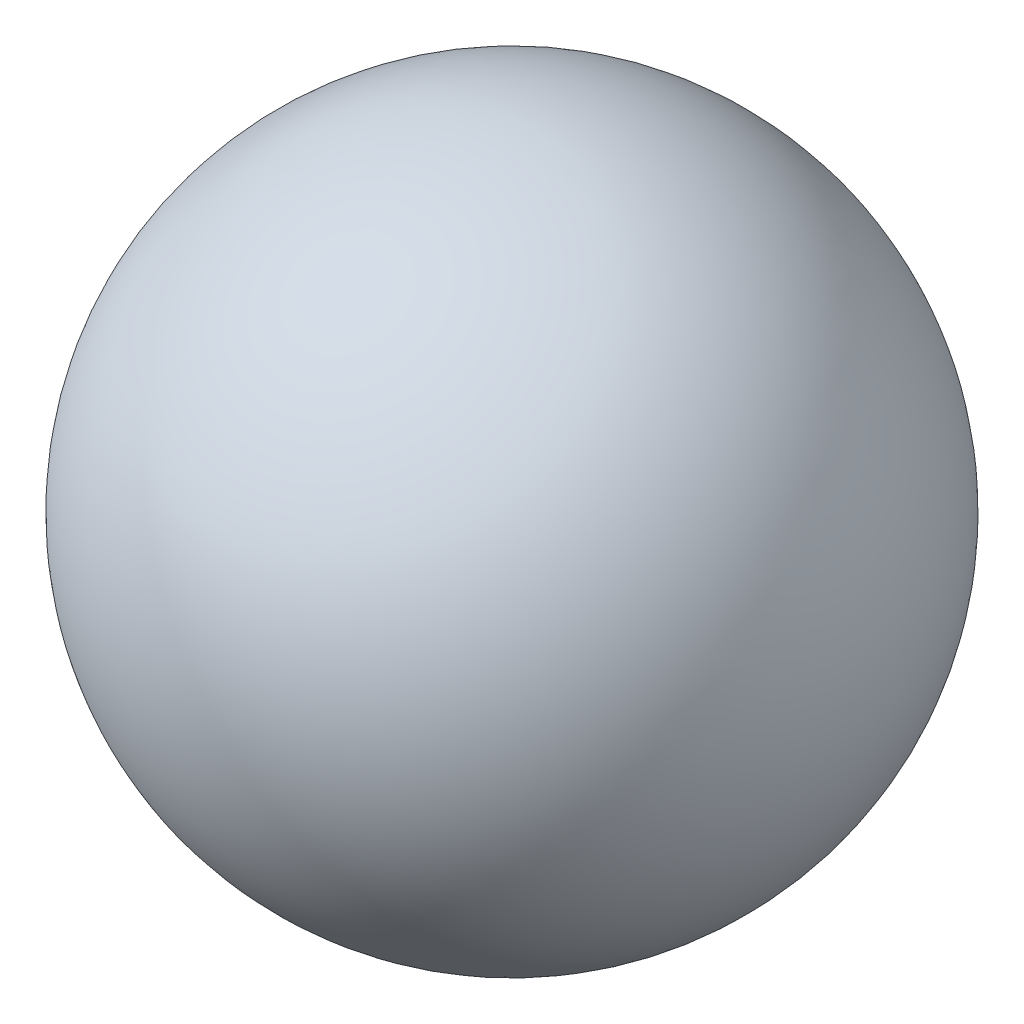
SolidWorks part; units mm, degrees
material "실리콘 고무"
ref_plane "정면" through (0, 0, 0) normal (0, 0, 1) x (1, 0, 0)
ref_plane "윗면" through (0, 0, 0) normal (0, 1, 0) x (1, 0, 0)
ref_plane "우측면" through (0, 0, 0) normal (1, 0, 0) x (0, 0, -1)
sketch "스케치1" plane through (0, 0, 0) normal (0, 1, 0) x (1, 0, 0)
  line L0 (0, 33.5) -> (0, -33.5) construction
  circle A0 centre (0, 0) radius 33.5
  circle A1 centre (0, 0) radius 30
  dimension "D1" = 67
  dimension "D2" = 60
revolve "회전2" add sketch "스케치1" angle 360 about L0 region at (-0.7491, 0, -31.75)
